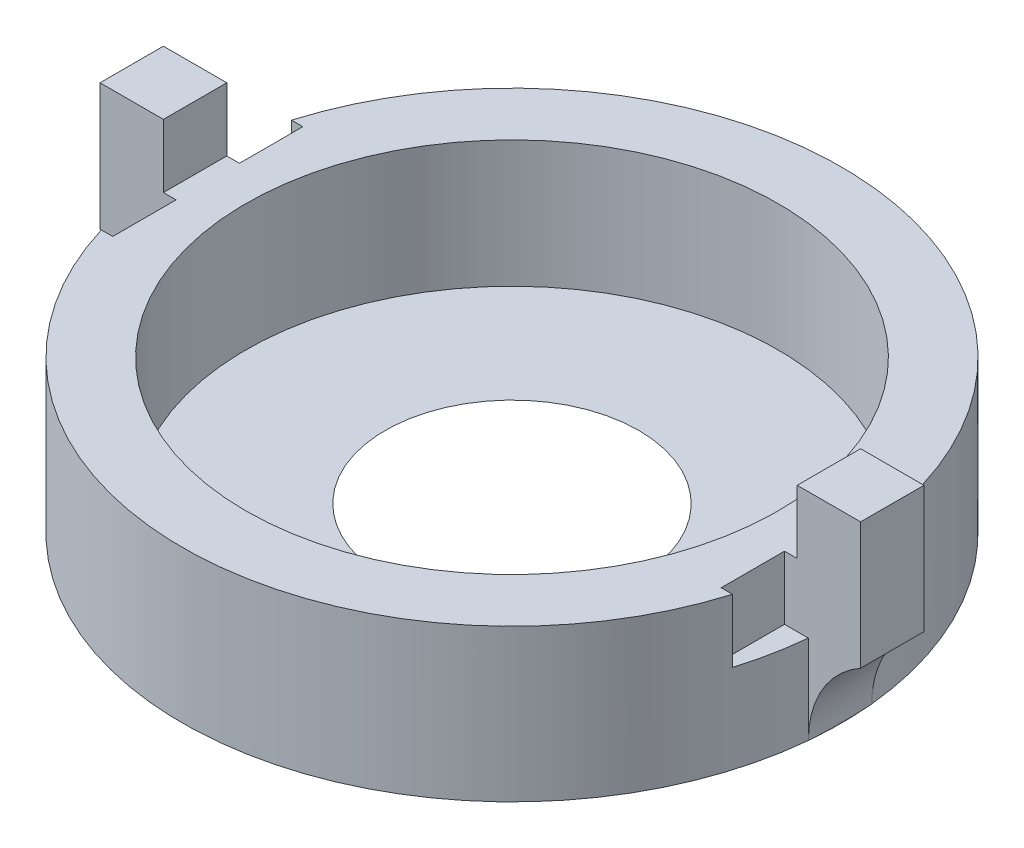
SolidWorks part; units mm, degrees
note: The reader was unsure of these and kept them because the rebuilt part matched: shared geometry of "Sketch1<3>", "Sketch3<2>", "Sketch6<3>".
ref_plane "Front Plane" through (0, 0, 0) normal (0, 0, 1) x (1, 0, 0)
ref_plane "Top Plane" through (0, 0, 0) normal (0, 1, 0) x (1, 0, 0)
ref_plane "Right Plane" through (0, 0, 0) normal (1, 0, 0) x (0, 0, -1)
sketch "Sketch1" plane through (0, 0, 0) normal (0, 1, 0) x (1, 0, 0)
  circle A0 centre (0, 0) radius 10
  circle A1 centre (0, 0) radius 26
  circle A2 centre (0, 0) radius 16.05
  circle A3 centre (0, 0) radius 21
  dimension "D1" = 52
  dimension "D2" = 20
  dimension "D3" = 32.1
  dimension "D4" = 5
extrude "Boss-Extrude1" add sketch "Sketch1" along normal blind 2 contours A1 A3 | A3 A2 | A2 A0
extrude "Boss-Extrude2" add sketch "Sketch1<3>" along normal blind 12 contours A1 A3
sketch "Sketch1<3>" plane through (0, 0, 0) normal (0, 1, 0) x (1, 0, 0) same geometry as "Sketch1"
fillet "Fillet1" radius 15 1 edges at (0, 0, 10)
sketch "Sketch3" plane through (0, 0, 0) normal (1, 0, 0) x (0, 0, -1)
  line L2 (-2.5, 7) -> (2.5, 7)
  line L6 (-2.5, 17) -> (2.5, 17)
  line L7 (2.5, 17) -> (2.5, 7)
  line L9 (-2.5, 17) -> (-2.5, 7)
  point P0 (0, 7)
  point P1 (0, 17)
  dimension "D1" = 10
  dimension "D2" = 5
extrude "Boss-Extrude3" add sketch "Sketch3" against normal blind 5 from offset 25 offset against normal yes
fillet "Fillet3" radius 8 1 edges at (-26, 7, 0)
extrude "Boss-Extrude4" add sketch "Sketch3<2>" along normal blind 5 from offset 25
sketch "Sketch3<2>" plane through (0, 0, 0) normal (1, 0, 0) x (0, 0, -1) same geometry as "Sketch3"
fillet "Fillet5" radius 8 3 edges at (26, 7, 0) (27.9398, 7, -2.5) (27.9398, 7, 2.5)
sketch "Sketch6" plane through (0, 0, 0) normal (1, 0, 0) x (0, 0, -1)
  line L0 (-2.5, 17) -> (7.5, 17)
  line L1 (2.5, 17) -> (2.5, 7)
  line L2 (7.5, 7) -> (-2.5, 7)
  line L3 (-2.5, 7) -> (-2.5, 17)
  line L4 (7.5, 7) -> (7.5, 17)
  line L5 (-12.5, 7) -> (-2.5, 7)
  line L6 (-7.5, 17) -> (-7.5, 7)
  line L7 (-2.5, 17) -> (-12.5, 17)
extrude "Cut-Extrude1" cut sketch "Sketch6" along normal blind 6 from offset 24 contours L3 L7 L6 L5 | L2 L4 L0 L1
extrude "Cut-Extrude2" cut sketch "Sketch6<3>" against normal blind 6 from offset 24 contours L3 L7 L6 L5 | L2 L4 L0 L1 offset against normal yes
sketch "Sketch6<3>" plane through (0, 0, 0) normal (1, 0, 0) x (0, 0, -1) same geometry as "Sketch6"
